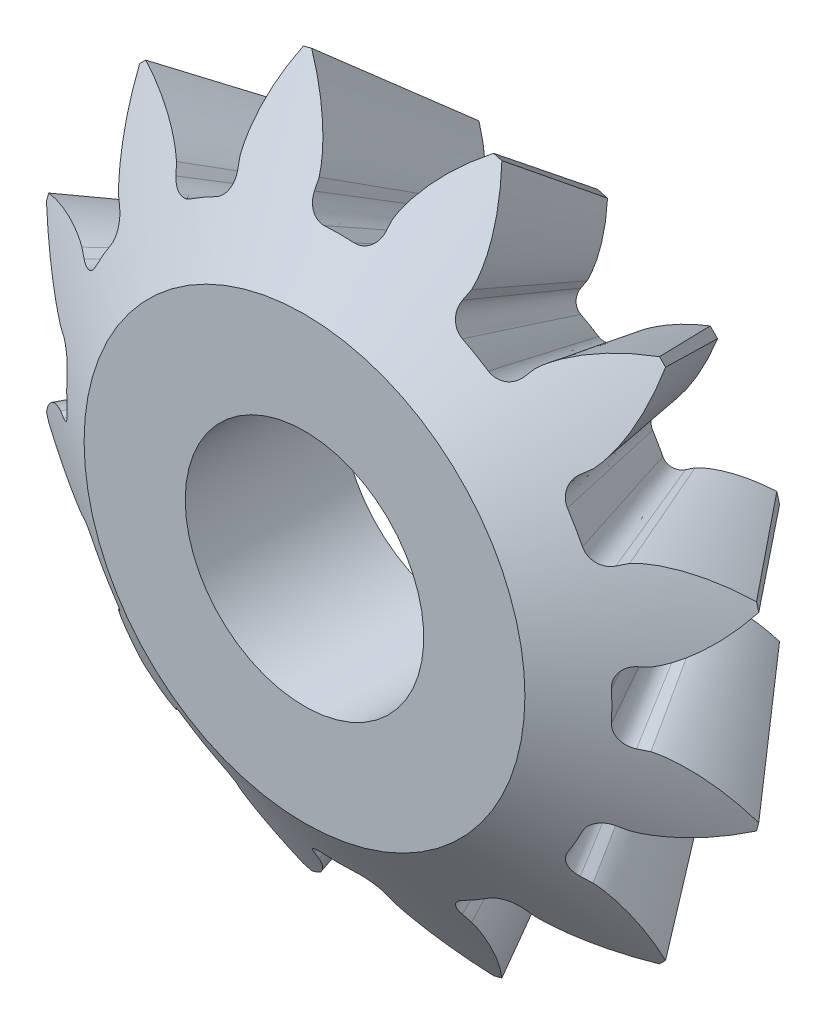
SolidWorks part; units mm, degrees
ref_plane "Front Plane" through (0, 0, 0) normal (0, 0, 1) x (1, 0, 0)
ref_plane "Top Plane" through (0, 0, 0) normal (0, 1, 0) x (1, 0, 0)
ref_plane "Right Plane" through (0, 0, 0) normal (1, 0, 0) x (0, 0, -1)
ref_axis "Gear Axis" through (0, 0, -0.9465) along (0, 0, 1)
sketch "Blank Sketch" plane through (0, 0, 0) normal (0, 1, 0) x (1, 0, 0)
  line L0 (0, 0) -> (0, -18.9291) construction
  line L1 (0, 0) -> (10.5, -15.75) construction
  line L2 (0, 0) -> (7.1718, -10.7577) construction
  line L3 (4.4944, -12.5426) -> (8.3337, -9.9831)
  line L4 (8.3337, -9.9831) -> (12.3282, -14.5312)
  line L5 (12.3282, -14.5312) -> (7.3923, -17.8218)
  line L6 (7.3923, -17.8218) -> (4, -17.8218)
  line L7 (4, -17.8218) -> (4, -12.5426)
  line L8 (4, -12.5426) -> (4.4944, -12.5426)
  line L9 (10.5, -15.75) -> (12.3282, -14.5312) construction
  line L10 (10.5, -15.75) -> (7.3923, -17.8218) construction
  line L11 (7.1718, -10.7577) -> (4.4944, -12.5426) construction
  dimension "Axis" = 18.9291
  dimension "Cone" = 33.69
  dimension "Heel" = 18.9291
  dimension "Toe Cone" = 33.69
  dimension "Toe" = 12.9291
  dimension "Heel Square" = 90
  dimension "Addendum" = 2.1972
  dimension "Root Square" = 90
  dimension "Heel Rim" = 3.735
  dimension "Toe Square" = 90
  dimension "Toe Rim" = 3.2178
  dimension "Front Square" = 90
  dimension "Face" = 7.602
  dimension "Back" = 3.3923
  dimension "Front" = 0.4944
revolve "Blank" add sketch "Blank Sketch" angle 360 about L0
sketch "Cone Sketch" plane through (0, 0, 0) normal (0, 1, 0) x (1, 0, 0)
  line L0 (0, 0) -> (0, -18.9291) construction
  line L1 (0, 0) -> (11.4707, -17.2061)
  line L2 (0, 0) -> (6.2011, -9.3016)
  dimension "Axis" = 18.9291
  dimension "Toe Cone" = 33.69
  dimension "Heel Cone" = 33.69
  dimension "Heel" = 20.6791
  dimension "Toe" = 11.1791
ref_plane "Heel Plane" through (11.4707, 0, 17.2061) normal (0.5547, 0, 0.8321) x (0.8321, 0, -0.5547)
ref_plane "Toe Plane" through (6.2011, 0, 9.3016) normal (0.5547, 0, 0.8321) x (0.8321, 0, -0.5547)
sketch "Heel Section Sketch" plane through (11.4707, 0, 17.2061) normal (0.5547, 0, 0.8321) x (0.8321, 0, -0.5547)
  line L0 (0, 0) -> (-13.7861, 0) construction
  line L1 (-0.7622, 1.3456) -> (-1.1442, 1.3061)
  line L2 (-0.7622, -1.3456) -> (-1.1442, -1.3061)
  line L3 (3.4799, 5.4252) -> (3.4799, -5.4252)
  arc A0 (-1.1442, 1.3061) -> (-1.7953, 0.5502) centre (-1.0695, 0.5835) ccw
  arc A1 (-1.7953, -0.5502) -> (-1.1442, -1.3061) centre (-1.0695, -0.5835) ccw
  arc A2 (-1.7953, -0.5502) -> (-1.7953, 0.5502) centre (-13.7861, 0) ccw
  spline S0 degree 4 poles (-0.8755, 1.3209) (-0.8422, 1.3272) (-0.7846, 1.3393) (-0.7251, 1.3546) (-0.5923, 1.3942) (-0.4776, 1.4361) (-0.3248, 1.4967) (-0.173, 1.5666) (-0.0032, 1.6517) (0.1588, 1.7418) (0.3202, 1.8382) (0.4769, 1.9391) (0.6448, 2.0542) (0.8459, 2.2015) (1.0788, 2.3866) (1.3375, 2.6104) (1.6097, 2.8698) (1.8683, 3.1361) (2.1196, 3.4193) (2.3543, 3.701) (2.5878, 4.0088) (2.7954, 4.2952) (3.0183, 4.6365) (3.1887, 4.9053) (3.4083, 5.2912) (3.5231, 5.5036) (3.661, 5.7721) (3.7187, 5.8918) (3.7527, 5.9625) knots 0 0 0 0 0 0.016753 0.031571 0.050064 0.068907 0.096646 0.124386 0.152126 0.179865 0.207605 0.235344 0.263084 0.300343 0.355823 0.411302 0.466781 0.52226 0.577739 0.633218 0.688697 0.744176 0.799656 0.855135 0.910614 0.955307 1 1 1 1 1 construction
  spline S1 degree 4 poles (-0.7622, 1.3456) (-0.7406, 1.3511) (-0.6928, 1.3642) (-0.5923, 1.3942) (-0.4776, 1.4361) (-0.3248, 1.4967) (-0.173, 1.5666) (-0.0032, 1.6517) (0.1588, 1.7418) (0.3202, 1.8382) (0.4769, 1.9391) (0.6448, 2.0542) (0.8459, 2.2015) (1.0788, 2.3866) (1.3375, 2.6104) (1.6097, 2.8698) (1.8683, 3.1361) (2.1196, 3.4193) (2.3543, 3.701) (2.5878, 4.0088) (2.7954, 4.2952) (3.0183, 4.6365) (3.1887, 4.9053) (3.3618, 5.2095) (3.4403, 5.3516) (3.4799, 5.4252) knots 0.016753 0.016753 0.016753 0.016753 0.016753 0.031571 0.050064 0.068907 0.096646 0.124386 0.152126 0.179865 0.207605 0.235344 0.263084 0.300343 0.355823 0.411302 0.466781 0.52226 0.577739 0.633218 0.688697 0.744176 0.799656 0.855135 0.910614 0.910614 0.910614 0.910614 0.910614
  spline S2 degree 4 poles (-0.8755, -1.3209) (-0.8422, -1.3272) (-0.7846, -1.3393) (-0.7251, -1.3546) (-0.5923, -1.3942) (-0.4776, -1.4361) (-0.3248, -1.4967) (-0.173, -1.5666) (-0.0032, -1.6517) (0.1588, -1.7418) (0.3202, -1.8382) (0.4769, -1.9391) (0.6448, -2.0542) (0.8459, -2.2015) (1.0788, -2.3866) (1.3375, -2.6104) (1.6097, -2.8698) (1.8683, -3.1361) (2.1196, -3.4193) (2.3543, -3.701) (2.5878, -4.0088) (2.7954, -4.2952) (3.0183, -4.6365) (3.1887, -4.9053) (3.4083, -5.2912) (3.5231, -5.5036) (3.661, -5.7721) (3.7187, -5.8918) (3.7527, -5.9625) knots 0 0 0 0 0 0.016753 0.031571 0.050064 0.068907 0.096646 0.124386 0.152126 0.179865 0.207605 0.235344 0.263084 0.300343 0.355823 0.411302 0.466781 0.52226 0.577739 0.633218 0.688697 0.744176 0.799656 0.855135 0.910614 0.955307 1 1 1 1 1 construction
  spline S3 degree 4 poles (-0.7622, -1.3456) (-0.7406, -1.3511) (-0.6928, -1.3642) (-0.5923, -1.3942) (-0.4776, -1.4361) (-0.3248, -1.4967) (-0.173, -1.5666) (-0.0032, -1.6517) (0.1588, -1.7418) (0.3202, -1.8382) (0.4769, -1.9391) (0.6448, -2.0542) (0.8459, -2.2015) (1.0788, -2.3866) (1.3375, -2.6104) (1.6097, -2.8698) (1.8683, -3.1361) (2.1196, -3.4193) (2.3543, -3.701) (2.5878, -4.0088) (2.7954, -4.2952) (3.0183, -4.6365) (3.1887, -4.9053) (3.3618, -5.2095) (3.4403, -5.3516) (3.4799, -5.4252) knots 0.016753 0.016753 0.016753 0.016753 0.016753 0.031571 0.050064 0.068907 0.096646 0.124386 0.152126 0.179865 0.207605 0.235344 0.263084 0.300343 0.355823 0.411302 0.466781 0.52226 0.577739 0.633218 0.688697 0.744176 0.799656 0.855135 0.910614 0.910614 0.910614 0.910614 0.910614
  dimension "Root" = 12.0035
  dimension "Fillet" = 0.7265
  dimension "Centre" = 13.7861
sketch "Toe Section Sketch" plane through (6.2011, 0, 9.3016) normal (0.5547, 0, 0.8321) x (0.8321, 0, -0.5547)
  line L0 (0, 0) -> (-7.4528, 0) construction
  line L1 (-0.4121, 0.7274) -> (-0.6186, 0.7061)
  line L2 (-0.4121, -0.7274) -> (-0.6186, -0.7061)
  line L3 (1.8812, 2.9329) -> (1.8812, -2.9329)
  arc A0 (-0.6186, 0.7061) -> (-0.9705, 0.2974) centre (-0.5782, 0.3154) ccw
  arc A1 (-0.9705, -0.2974) -> (-0.6186, -0.7061) centre (-0.5782, -0.3154) ccw
  arc A2 (-0.9705, -0.2974) -> (-0.9705, 0.2974) centre (-7.4528, 0) ccw
  spline S0 degree 4 poles (-0.4733, 0.7141) (-0.4553, 0.7175) (-0.4241, 0.724) (-0.392, 0.7323) (-0.3202, 0.7537) (-0.2582, 0.7764) (-0.1756, 0.8091) (-0.0935, 0.8469) (-0.0017, 0.8929) (0.0858, 0.9416) (0.1731, 0.9937) (0.2578, 1.0483) (0.3486, 1.1105) (0.4573, 1.1901) (0.5832, 1.2902) (0.7231, 1.4112) (0.8702, 1.5514) (1.01, 1.6954) (1.1459, 1.8485) (1.2727, 2.0008) (1.399, 2.1671) (1.5112, 2.322) (1.6317, 2.5065) (1.7238, 2.6518) (1.8425, 2.8604) (1.9046, 2.9753) (1.9791, 3.1204) (2.0103, 3.1851) (2.0287, 3.2233) knots 0 0 0 0 0 0.016753 0.031571 0.050064 0.068907 0.096646 0.124386 0.152126 0.179865 0.207605 0.235344 0.263084 0.300343 0.355823 0.411302 0.466781 0.52226 0.577739 0.633218 0.688697 0.744176 0.799656 0.855135 0.910614 0.955307 1 1 1 1 1 construction
  spline S1 degree 4 poles (-0.4121, 0.7274) (-0.4004, 0.7304) (-0.3745, 0.7375) (-0.3202, 0.7537) (-0.2582, 0.7764) (-0.1756, 0.8091) (-0.0935, 0.8469) (-0.0017, 0.8929) (0.0858, 0.9416) (0.1731, 0.9937) (0.2578, 1.0483) (0.3486, 1.1105) (0.4573, 1.1901) (0.5832, 1.2902) (0.7231, 1.4112) (0.8702, 1.5514) (1.01, 1.6954) (1.1459, 1.8485) (1.2727, 2.0008) (1.399, 2.1671) (1.5112, 2.322) (1.6317, 2.5065) (1.7238, 2.6518) (1.8174, 2.8163) (1.8598, 2.8931) (1.8812, 2.9329) knots 0.016753 0.016753 0.016753 0.016753 0.016753 0.031571 0.050064 0.068907 0.096646 0.124386 0.152126 0.179865 0.207605 0.235344 0.263084 0.300343 0.355823 0.411302 0.466781 0.52226 0.577739 0.633218 0.688697 0.744176 0.799656 0.855135 0.910614 0.910614 0.910614 0.910614 0.910614
  spline S2 degree 4 poles (-0.4733, -0.7141) (-0.4553, -0.7175) (-0.4241, -0.724) (-0.392, -0.7323) (-0.3202, -0.7537) (-0.2582, -0.7764) (-0.1756, -0.8091) (-0.0935, -0.8469) (-0.0017, -0.8929) (0.0858, -0.9416) (0.1731, -0.9937) (0.2578, -1.0483) (0.3486, -1.1105) (0.4573, -1.1901) (0.5832, -1.2902) (0.7231, -1.4112) (0.8702, -1.5514) (1.01, -1.6954) (1.1459, -1.8485) (1.2727, -2.0008) (1.399, -2.1671) (1.5112, -2.322) (1.6317, -2.5065) (1.7238, -2.6518) (1.8425, -2.8604) (1.9046, -2.9753) (1.9791, -3.1204) (2.0103, -3.1851) (2.0287, -3.2233) knots 0 0 0 0 0 0.016753 0.031571 0.050064 0.068907 0.096646 0.124386 0.152126 0.179865 0.207605 0.235344 0.263084 0.300343 0.355823 0.411302 0.466781 0.52226 0.577739 0.633218 0.688697 0.744176 0.799656 0.855135 0.910614 0.955307 1 1 1 1 1 construction
  spline S3 degree 4 poles (-0.4121, -0.7274) (-0.4004, -0.7304) (-0.3745, -0.7375) (-0.3202, -0.7537) (-0.2582, -0.7764) (-0.1756, -0.8091) (-0.0935, -0.8469) (-0.0017, -0.8929) (0.0858, -0.9416) (0.1731, -0.9937) (0.2578, -1.0483) (0.3486, -1.1105) (0.4573, -1.1901) (0.5832, -1.2902) (0.7231, -1.4112) (0.8702, -1.5514) (1.01, -1.6954) (1.1459, -1.8485) (1.2727, -2.0008) (1.399, -2.1671) (1.5112, -2.322) (1.6317, -2.5065) (1.7238, -2.6518) (1.8174, -2.8163) (1.8598, -2.8931) (1.8812, -2.9329) knots 0.016753 0.016753 0.016753 0.016753 0.016753 0.031571 0.050064 0.068907 0.096646 0.124386 0.152126 0.179865 0.207605 0.235344 0.263084 0.300343 0.355823 0.411302 0.466781 0.52226 0.577739 0.633218 0.688697 0.744176 0.799656 0.855135 0.910614 0.910614 0.910614 0.910614 0.910614
  dimension "Root" = 6.4891
  dimension "Fillet" = 0.3927
  dimension "Centre" = 7.4528
loft "Tooth Space" cut profiles "Heel Section Sketch", "Toe Section Sketch"
pattern_circular "Teeth" count 12 over 360 about axis through (0, 0, -0.9465) along (0, 0, 1) of "Tooth Space"
equation "\"No. of Teeth\"= 12"
equation "\"Module\"= 1.75"
equation "\"Bore Diameter\"= 8"
equation "\"Pressure Angle\"= 20"
equation "\"Shaft Angle\"= 90"
equation "\"Mate Teeth\"= 18"
equation "\"Pitch Cone Angle\"= IIF ( ( \"Mate Teeth\" / \"No. of Teeth\" + cos ( \"Shaft Angle\" ) ) > 0 , atn ( sin ( \"Shaft Angle\" ) / ( \"Mate Teeth\" / \"No. of Teeth\" + cos ( \"Shaft Angle\" ) ) ) , 180 + atn ( sin ( \"Shaft Angle\" ) / ( \"Mate Teeth\" / \"No. of Teeth\" + cos ( \"Shaft Angle\" ) ) ) )"
equation "\"Mate Cone Angle\"= \"Shaft Angle\" - \"Pitch Cone Angle\""
equation "\"Addendum\"= IIF ( \"No. of Teeth\" >= \"Mate Teeth\" , 0.54 * \"Module\" + 0.46 * \"Module\" / ( ( \"No. of Teeth\" * cos ( \"Mate Cone Angle\" ) ) / ( \"Mate Teeth\" * cos ( \"Pitch Cone Angle\" ) ) ) , 2 * \"Module\" - ( 0.54 * \"Module\" + 0.46 * \"Module\" / ( ( \"Mate Teeth\" * cos ( \"Pitch Cone Angle\" ) ) / ( \"No. of Teeth\" * cos ( \"Mate Cone Angle\" ) ) ) ) )"
equation "\"Outer Diameter\"= \"No. of Teeth\" * \"Module\" + 2 * \"Addendum\" * cos ( \"Pitch Cone Angle\" )"
equation "\"Pitch Diameter\"= \"No. of Teeth\" * \"Module\""
equation "\"Backlash\"= 0.3 * \"Module\""
equation "\"Arc Length\"= ( ( \"Module\" * pi ) / 2 + \"Backlash\" - 2 * ( \"Addendum\" - \"Module\" ) * tan ( \"Pressure Angle\" ) )"
equation "\"Fillet Radius\"= 0.38 * \"Module\""
equation "\"Mate Addendum\"= 2 * \"Module\" - \"Addendum\""
equation "\"Dedendum\"= 2.188 * \"Module\" - \"Addendum\""
equation "\"Tooth Depth\"= \"Addendum\" + \"Dedendum\""
equation "\"Mate Dedendum\"= 2.188 * \"Module\" - \"Mate Addendum\""
equation "\"Face Width\"= 6"
equation "\"Cone Distance\"= \"Pitch Diameter\" / ( 2 * sin ( \"Pitch Cone Angle\" ) )"
equation "\"Dedendum Angle\"= atn ( \"Dedendum\" / \"Cone Distance\" )"
equation "\"Mate Dedendum Angle\"= atn ( \"Mate Dedendum\" / \"Cone Distance\" )"
equation "\"Face Angle\"= \"Pitch Cone Angle\" + \"Mate Dedendum Angle\""
equation "\"Root Angle\"= \"Pitch Cone Angle\" - \"Dedendum Angle\""
equation "\"Overrun\"= \"Module\""
equation "\"Back Cone Pitch Diameter\"= \"Pitch Diameter\" / cos ( \"Pitch Cone Angle\" )"
equation "\"Back Cone Outer Diameter\"= \"Back Cone Pitch Diameter\" + 2 * \"Addendum\""
equation "\"Root Diameter\"= \"Back Cone Outer Diameter\" - 2 * \"Tooth Depth\""
equation "\"Base Diameter\"= \"Back Cone Pitch Diameter\" * cos ( \"Pressure Angle\" )"
equation "\"Base Radius\"= \"Base Diameter\" / 2"
equation "\"Tooth Thickness\"= \"Module\" * pi - \"Arc Length\""
equation "\"Half Space Angle\"= ( \"Arc Length\" / \"Back Cone Pitch Diameter\" ) * 180 / pi"
equation "\"Involute Fn\"= tan ( \"Pressure Angle\" ) - \"Pressure Angle\" * pi / 180"
equation "\"Flank Offset\"= \"Arc Length\" / \"Back Cone Pitch Diameter\" - \"Involute Fn\""
equation "\"Tip Cap Diameter\"= \"Back Cone Outer Diameter\" + 2 * \"Module\""
equation "\"Flank Start Diameter\"= IIF ( \"Base Diameter\" >= ( \"Root Diameter\" + 3 * \"Fillet Radius\" ) , \"Base Diameter\" , \"Root Diameter\" + 3 * \"Fillet Radius\" )"
equation "\"Involute t1\"= ( abs ( ( \"Flank Start Diameter\" / \"Base Diameter\" ) ^ 2 - 1 ) ) ^ 0.5"
equation "\"Involute t2\"= ( abs ( ( \"Tip Cap Diameter\" / \"Base Diameter\" ) ^ 2 - 1 ) ) ^ 0.5"
equation "\"Flank Arc Radius\"= ( \"Back Cone Pitch Diameter\" / 2 ) * sin ( \"Pressure Angle\" )"
equation "\"Flank Centre Angle\"= \"Half Space Angle\" + \"Pressure Angle\""
equation "\"Heel Distance\"= \"Cone Distance\" + \"Overrun\""
equation "\"Toe Distance\"= \"Cone Distance\" - \"Face Width\" - \"Overrun\""
equation "\"Heel Scale\"= \"Heel Distance\" / \"Cone Distance\""
equation "\"Toe Scale\"= \"Toe Distance\" / \"Cone Distance\""
equation "\"Heel Virtual Radius\"= \"Heel Distance\" * tan ( \"Pitch Cone Angle\" )"
equation "\"Toe Virtual Radius\"= \"Toe Distance\" * tan ( \"Pitch Cone Angle\" )"
equation "\"Axis@Blank Sketch\"= \"Cone Distance\""
equation "\"Cone@Blank Sketch\"= \"Pitch Cone Angle\""
equation "\"Heel@Blank Sketch\"= \"Cone Distance\""
equation "\"Toe Cone@Blank Sketch\"= \"Pitch Cone Angle\""
equation "\"Toe@Blank Sketch\"= \"Cone Distance\" - \"Face Width\""
equation "\"Addendum@Blank Sketch\"= \"Addendum\""
equation "\"Heel Rim@Blank Sketch\"= \"Dedendum\" + \"Module\" / cos ( \"Pitch Cone Angle\" )"
equation "\"Toe Rim@Blank Sketch\"= \"Dedendum\" - \"Face Width\" * tan ( \"Dedendum Angle\" ) + \"Module\" / cos ( \"Pitch Cone Angle\" )"
equation "\"Face@Blank Sketch\"= \"Mate Dedendum Angle\""
equation "\"Back@Blank Sketch\"= \"Cone Distance\" * sin ( \"Pitch Cone Angle\" ) - \"Dedendum\" * cos ( \"Pitch Cone Angle\" ) - \"Module\" - \"Bore Diameter\" / 2"
equation "\"Front@Blank Sketch\"= ( \"Cone Distance\" - \"Face Width\" ) * sin ( \"Pitch Cone Angle\" ) - ( \"Dedendum\" - \"Face Width\" * tan ( \"Dedendum Angle\" ) + \"Module\" / cos ( \"Pitch Cone Angle\" ) ) * cos ( \"Pitch Cone Angle\" ) - \"Bore Diameter\" / 2"
equation "\"Axis@Cone Sketch\"= \"Cone Distance\""
equation "\"Heel Cone@Cone Sketch\"= \"Pitch Cone Angle\""
equation "\"Heel@Cone Sketch\"= \"Heel Distance\""
equation "\"Toe Cone@Cone Sketch\"= \"Pitch Cone Angle\""
equation "\"Toe@Cone Sketch\"= \"Toe Distance\""
equation "\"Centre@Heel Section Sketch\"= \"Heel Virtual Radius\""
equation "\"Root@Heel Section Sketch\"= ( \"Root Diameter\" / 2 ) * \"Heel Scale\""
equation "\"Fillet@Heel Section Sketch\"= ( \"Fillet Radius\" ) * \"Heel Scale\""
equation "\"Centre@Toe Section Sketch\"= \"Toe Virtual Radius\""
equation "\"Root@Toe Section Sketch\"= ( \"Root Diameter\" / 2 ) * \"Toe Scale\""
equation "\"Fillet@Toe Section Sketch\"= ( \"Fillet Radius\" ) * \"Toe Scale\""
equation "\"Count@Teeth\"= \"No. of Teeth\""
